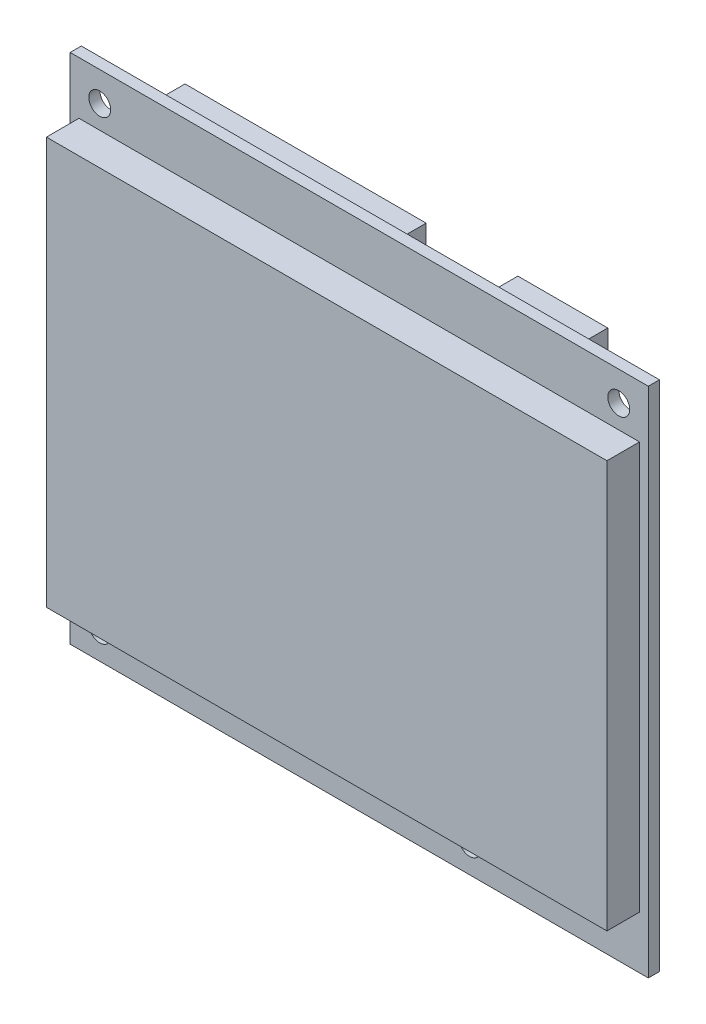
SolidWorks part; units mm, degrees
ref_plane "Front Plane" through (0, 0, 0) normal (0, 0, 1) x (1, 0, 0)
ref_plane "Top Plane" through (0, 0, 0) normal (0, 1, 0) x (1, 0, 0)
ref_plane "Right Plane" through (0, 0, 0) normal (1, 0, 0) x (0, 0, -1)
sketch "Sketch1" plane through (0, 0, 0) normal (0, 0, -1) x (-1, 0, 0)
  line L0 (42.4, 0) -> (43.6432, 0) construction
  line L1 (-32.4, -24.3) -> (32.4, -24.3) construction
  line L2 (-32.4, -24.3) -> (-32.4, 24.3) construction
  line L3 (-32.4, 24.3) -> (32.4, 24.3) construction
  line L4 (32.4, -24.3) -> (32.4, 24.3) construction
  line L5 (-32.4, -24.3) -> (32.4, 24.3) construction
  line L6 (-32.4, 24.3) -> (32.4, -24.3) construction
  line L7 (-36.8, 28.77) -> (42.4, 28.77) construction
  line L8 (-36.8, 28.77) -> (-36.8, -28.77) construction
  line L9 (-36.8, -28.77) -> (42.4, -28.77) construction
  line L10 (42.4, 28.77) -> (42.4, -28.77) construction
  line L11 (-38.0432, 36.2077) -> (43.6432, 36.2077)
  line L12 (-38.0432, 36.2077) -> (-38.0432, -36.2077)
  line L13 (-38.0432, -36.2077) -> (43.6432, -36.2077)
  line L14 (43.6432, 36.2077) -> (43.6432, -36.2077)
  line L15 (-36.8, 0) -> (-38.0432, 0) construction
  line L16 (2.8, -28.77) -> (2.8, -36.2077) construction
  line L17 (2.8, 28.77) -> (2.8, 36.2077) construction
  point P0 (0, 0)
  dimension "D1" = 64.8
  dimension "D2" = 48.6
  dimension "D3" = 4.4
  dimension "D4" = 4.47
  dimension "D5" = 57.54
  dimension "D6" = 79.2
  dimension "D8" = 72.4154
  dimension "D9" = 81.6864
extrude "Boss-Extrude1" add sketch "Sketch1" along normal blind 1.5748
sketch "Sketch2" plane through (0, 0, 0) normal (0, 0, -1) x (-1, 0, 0)
  line L1 (-36.8, -28.77) -> (42.4, -28.77)
  line L2 (-36.8, -28.77) -> (-36.8, 28.77)
  line L3 (-36.8, 28.77) -> (42.4, 28.77)
  line L4 (42.4, -28.77) -> (42.4, 28.77)
  line L10 (-32.4, -24.3) -> (32.4, -24.3) construction
  line L11 (-32.4, -24.3) -> (-32.4, 24.3) construction
  line L12 (-32.4, 24.3) -> (32.4, 24.3) construction
  line L13 (32.4, -24.3) -> (32.4, 24.3) construction
  line L14 (-32.4, -24.3) -> (32.4, 24.3) construction
  line L15 (-32.4, 24.3) -> (32.4, -24.3) construction
  point P0 (0, 0)
  point P14 (0, 0)
  dimension "D1" = 57.54
  dimension "D2" = 79.2
  dimension "D3" = 4.4
  dimension "D4" = 48.6
  dimension "D5" = 64.8
  dimension "D6" = 4.47
extrude "Boss-Extrude2" add sketch "Sketch2" against normal blind 4.6
sketch "Sketch3" plane through (0, 0, -1.5748) normal (0, 0, 1) x (1, 0, 0)
  line L1 (25.66, 33.8141) -> (12.96, 33.8141)
  line L2 (25.66, 33.8141) -> (25.66, 28.7341)
  line L3 (25.66, 28.7341) -> (12.96, 28.7341)
  line L4 (12.96, 33.8141) -> (12.96, 28.7341)
  line L6 (0, 33.8141) -> (-34.0711, 33.8141)
  line L7 (0, 33.8141) -> (0, 28.7341)
  line L8 (0, 28.7341) -> (-34.0711, 28.7341)
  line L9 (-34.0711, 33.8141) -> (-34.0711, 28.7341)
  line L10 (-34.0711, -29.1593) -> (0, -29.1593)
  line L11 (-34.0711, -29.1593) -> (-34.0711, -34.2393)
  line L12 (-34.0711, -34.2393) -> (0, -34.2393)
  line L13 (0, -29.1593) -> (0, -34.2393)
  dimension "D1" = 5.08
  dimension "D2" = 12.7
sketch "Sketch4" plane through (0, 0, -1.5748) normal (0, 0, -1) x (-1, 0, 0)
  line L0 (43.6432, 36.2077) -> (-38.0432, 36.2077) construction
  line L1 (-38.0432, 36.2077) -> (-38.0432, -36.2077) construction
  line L2 (43.6432, -36.2077) -> (43.6432, 36.2077) construction
  line L3 (-38.0432, -36.2077) -> (43.6432, -36.2077) construction
  circle A0 centre (39.4682, 32.0327) radius 1.55
  circle A1 centre (39.4682, -32.4077) radius 1.55
  circle A2 centre (-12.7918, -32.4077) radius 1.55
  circle A3 centre (-33.8682, 32.0327) radius 1.55
  dimension "D3" = 3.1
  dimension "D1" = 4.175
  dimension "D2" = 4.175
  dimension "D4" = 4.175
  dimension "D5" = 3.8
  dimension "D6" = 52.26
extrude "Cut-Extrude1" cut sketch "Sketch4" against normal through all
extrude "Boss-Extrude3" add sketch "Sketch3" against normal blind 5.08
sketch "Sketch5" plane through (0, 0, -1.5748) normal (0, 0, -1) x (-1, 0, 0)
  line L0 (19.4766, 13.5356) -> (30.7313, 2.2809)
  line L1 (30.7313, 2.2809) -> (19.4766, -8.9738)
  line L2 (19.4766, -8.9738) -> (8.2218, 2.2809)
  line L3 (8.2218, 2.2809) -> (19.4766, 13.5356)
  line L5 (-15.8477, -24.7973) -> (-26.991, -24.7973)
  line L6 (-15.8477, -24.7973) -> (-15.8477, -9.9767)
  line L7 (-15.8477, -9.9767) -> (-26.991, -9.9767)
  line L8 (-26.991, -24.7973) -> (-26.991, -9.9767)
  line L9 (-37.0611, -34.1253) -> (-31.3584, -34.1253)
  line L10 (-37.0611, -34.1253) -> (-37.0611, -35.0607)
  line L11 (-37.0611, -35.0607) -> (-31.3584, -35.0607)
  line L12 (-31.3584, -34.1253) -> (-31.3584, -35.0607)
extrude "Boss-Extrude4" add sketch "Sketch5" along normal blind 1
